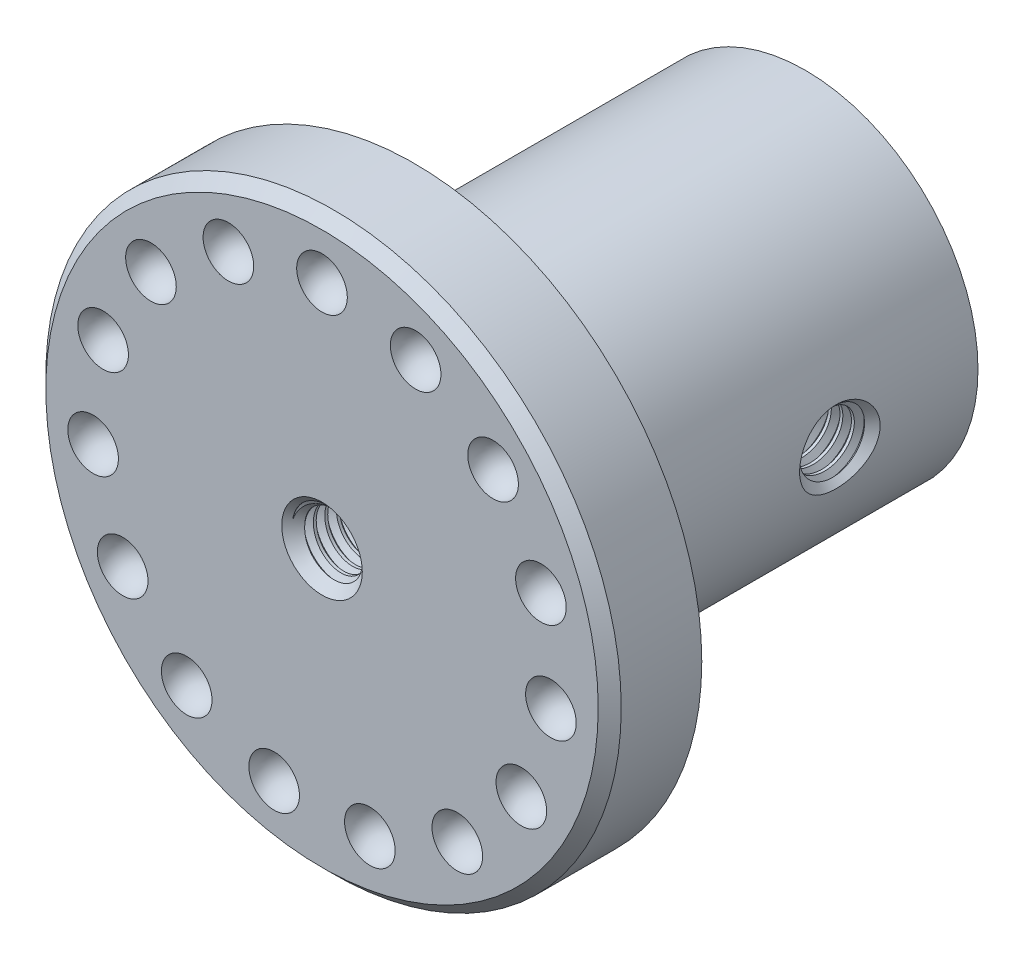
SolidWorks part; units mm, degrees
ref_plane "Front Plane" through (0, 0, 0) normal (0, 0, 1) x (1, 0, 0)
ref_plane "Top Plane" through (0, 0, 0) normal (0, 1, 0) x (1, 0, 0)
ref_plane "Right Plane" through (0, 0, 0) normal (1, 0, 0) x (0, 0, -1)
sketch "Sketch1" plane through (0, 0, 0) normal (0, 0, 1) x (1, 0, 0)
  circle A0 centre (0, 0) radius 12.5
  dimension "D1" = 25
extrude "Boss-Extrude1" add sketch "Sketch1" along normal blind 4
ref_axis "Axis1" through (0, 0, -0.35) along (0, 0, 1)
chamfer "Chamfer1" distance 0.5 angle 45 1 edges at (12.5, 0, 4)
ref_axis "Axis2" through (0, 14.0125, 4) along (0, -1, 0)
sketch "Sketch6" plane through (0, 0, 0) normal (1, 0, 0) x (0, 0, -1)
  line L0 (-4, 14.0125) -> (-4, -13.7625) construction
  line L1 (-4, 8.9) -> (-4, 11.1)
  line L2 (0, 12.5) -> (-3.5, 12.5) construction
  arc A0 (-4, 11.1) -> (-4, 8.9) centre (-4, 10) ccw
  dimension "D1" = 2.2
  dimension "D2" = 2.5
revolve "Cut-Revolve2" cut sketch "Sketch6" angle 360 about L1
pattern_circular "CirPattern1" count 15 over 360 about axis through (0, 0, 3.5) along (0, 0, -1) of "Cut-Revolve2"
sketch "Sketch7" plane through (0, 0, 4) normal (0, 0, 1) x (1, 0, 0)
  circle A0 centre (0, 0) radius 1.25
  dimension "D1" = 2.5
extrude "Cut-Extrude1" cut sketch "Sketch7" against normal through all
thread "Thread1" pitch 0.5 method cut profile "Thread Profile1" start angle 0, offset 1, length 0, pitch 0.5, diameter 2.5
ref_plane "Plane1" through (-1.25, 0, 5) normal (0, -1, 0) x (-1, 0, 0)
sketch "Thread Profile1" plane through (-1.25, 0, 5) normal (0, -1, 0) x (-1, 0, 0)
  line L0 (0, 0) -> (0, 0.5) construction
  line L1 (0, 0) -> (0.2706, 0.1562)
  line L2 (0.2706, 0.1562) -> (0.2706, 0.2187)
  line L3 (0.2706, 0.2187) -> (0, 0.375)
  line L4 (0.2706, 0.1875) -> (0, 0.1875) construction
  line L11 (0, 0) -> (0, 0.375)
  point P2 (0, 0)
  dimension "Pitch" = 0.5
  dimension "Profile_Angle" = 60
  dimension "Profile_Land" = 0.0625
  dimension "Profile_Height" = 0.2706
sketch "Sketch10" plane through (0, 0, 4) normal (0, 0, 1) x (1, 0, 0)
  circle A0 centre (0, 0) radius 1.75
  dimension "D1" = 3.5
extrude "Cut-Extrude2" cut sketch "Sketch10" against normal blind 10 draft 45 contours A0
sketch "Sketch11" plane through (0, 0, 0) normal (0, 0, -1) x (-1, 0, 0)
  circle A0 centre (0, 0) radius 7.5
  dimension "D1" = 15
extrude "Boss-Extrude2" add sketch "Sketch11" along normal blind 17 contours A0
sketch "Sketch12" plane through (0, 0, -17) normal (0, 0, -1) x (-1, 0, 0)
  circle A0 centre (0, 0) radius 2.5
  dimension "D1" = 5
extrude "Cut-Extrude3" cut sketch "Sketch12" against normal blind 15 contours A0
ref_plane "Plane2" through (7.5, 0, 0) normal (1, 0, 0) x (0, 0, -1)
sketch "Sketch13" plane through (7.5, 0, 0) normal (1, 0, 0) x (0, 0, -1)
  line L0 (17, -7.5) -> (17, 7.5) construction
  circle A0 centre (11, 0) radius 1.25
  dimension "D2" = 2.5
  dimension "D1" = 6
extrude "Cut-Extrude4" cut sketch "Sketch13" against normal up to next contours A0
thread "Thread2" pitch 0.5 method cut profile "Thread Profile2" start angle 0, offset 1, length 8, pitch 0.5, diameter 2.5
ref_plane "Plane3" through (8.5, 0, -9.75) normal (0, -1, 0) x (0, 0, 1)
sketch "Thread Profile2" plane through (8.5, 0, -9.75) normal (0, -1, 0) x (0, 0, 1)
  line L0 (0, 0) -> (0, 0.5) construction
  line L1 (0, 0) -> (0.2706, 0.1562)
  line L2 (0.2706, 0.1562) -> (0.2706, 0.2187)
  line L3 (0.2706, 0.2187) -> (0, 0.375)
  line L4 (0.2706, 0.1875) -> (0, 0.1875) construction
  line L11 (0, 0) -> (0, 0.375)
  point P2 (0, 0)
  dimension "Pitch" = 0.5
  dimension "Profile_Angle" = 60
  dimension "Profile_Land" = 0.0625
  dimension "Profile_Height" = 0.2706
sketch "Sketch16" plane through (7.5, 0, 0) normal (1, 0, 0) x (0, 0, -1)
  circle A0 centre (11, 0) radius 1.75
  point P2 (11, 0)
  dimension "D1" = 3.5
extrude "Cut-Extrude5" cut sketch "Sketch16" against normal blind 15 draft 45
